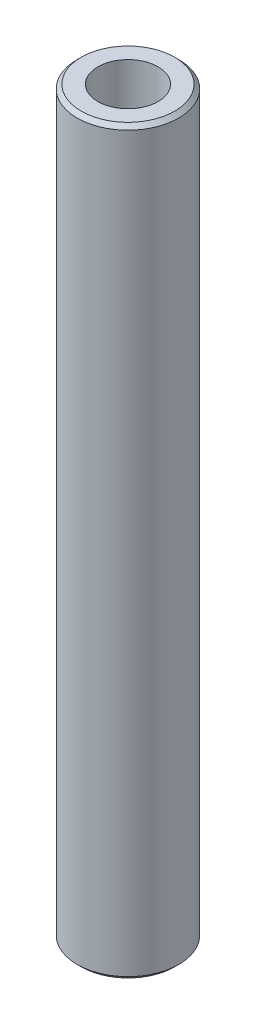
SolidWorks part; units mm, degrees
ref_plane "Front Plane" through (0, 0, 0) normal (0, 0, 1) x (1, 0, 0)
ref_plane "Top Plane" through (0, 0, 0) normal (0, 1, 0) x (1, 0, 0)
ref_plane "Right Plane" through (0, 0, 0) normal (1, 0, 0) x (0, 0, -1)
sketch "Sketch1" plane through (0, 0, 0) normal (0, 1, 0) x (1, 0, 0)
  circle A0 centre (0, 0) radius 37.5
  dimension "SHAFT_OD" = 75
extrude "Boss-Extrude1" add sketch "Sketch1" along normal blind 547.4925
sketch "Sketch2" plane through (0, 0, 0) normal (0, 1, 0) x (1, 0, 0)
  circle A0 centre (0, 0) radius 22.261
  dimension "BORE_D" = 44.5221
extrude "Cut-Extrude1" cut sketch "Sketch2" along normal through all
chamfer "Chamfer1" distance 2.9543 angle 45 2 edges at (0, 547.4925, 37.5) (0, 0, 37.5)
